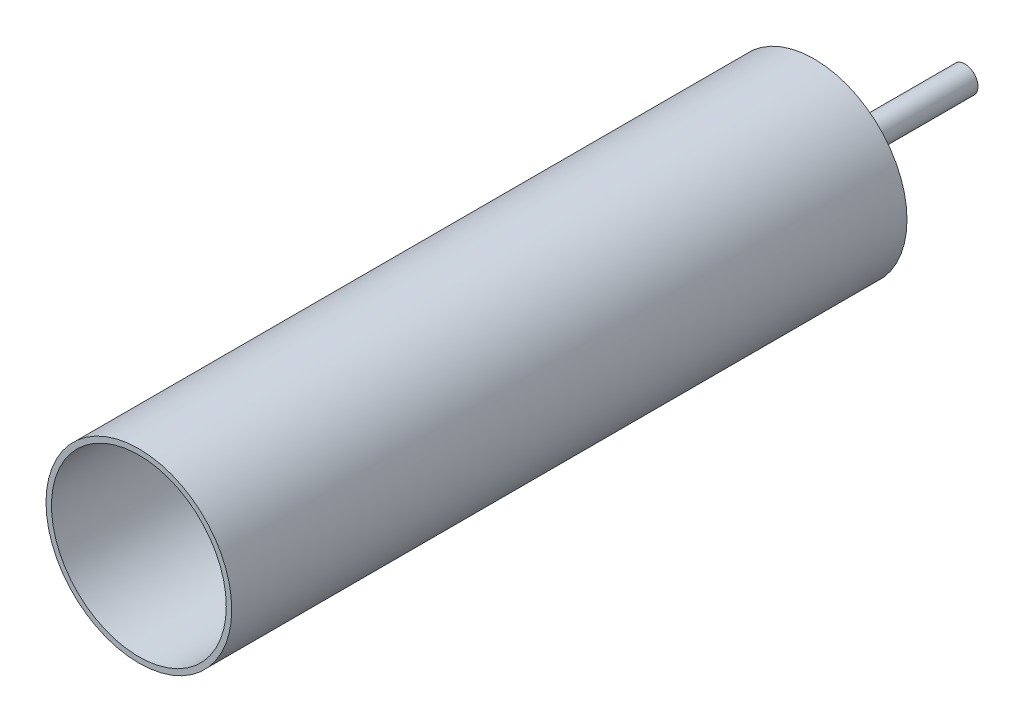
SolidWorks part; units mm, degrees
ref_plane "Front Plane" through (0, 0, 0) normal (0, 0, 1) x (1, 0, 0)
ref_plane "Top Plane" through (0, 0, 0) normal (0, 1, 0) x (1, 0, 0)
ref_plane "Right Plane" through (0, 0, 0) normal (1, 0, 0) x (0, 0, -1)
sketch "Sketch1" plane through (0, 0, 0) normal (0, 0, 1) x (1, 0, 0)
  circle A0 centre (0, 0) radius 21.59
  dimension "D1" = 43.18
extrude "Boss-Extrude1" add sketch "Sketch1" against normal blind 156.972
sketch "Sketch2" plane through (0, 0, -156.972) normal (0, 0, -1) x (-1, 0, 0)
  circle A0 centre (0, 0) radius 3.048
  dimension "D1" = 6.096
extrude "Boss-Extrude2" add sketch "Sketch2" along normal blind 35.052
sketch "Sketch5" plane through (0, 0, 0) normal (0, 0, 1) x (1, 0, 0)
  circle A0 centre (0, 0) radius 20.32
  dimension "D1" = 40.64
extrude "Cut-Extrude1" cut sketch "Sketch5" against normal blind 152.4
